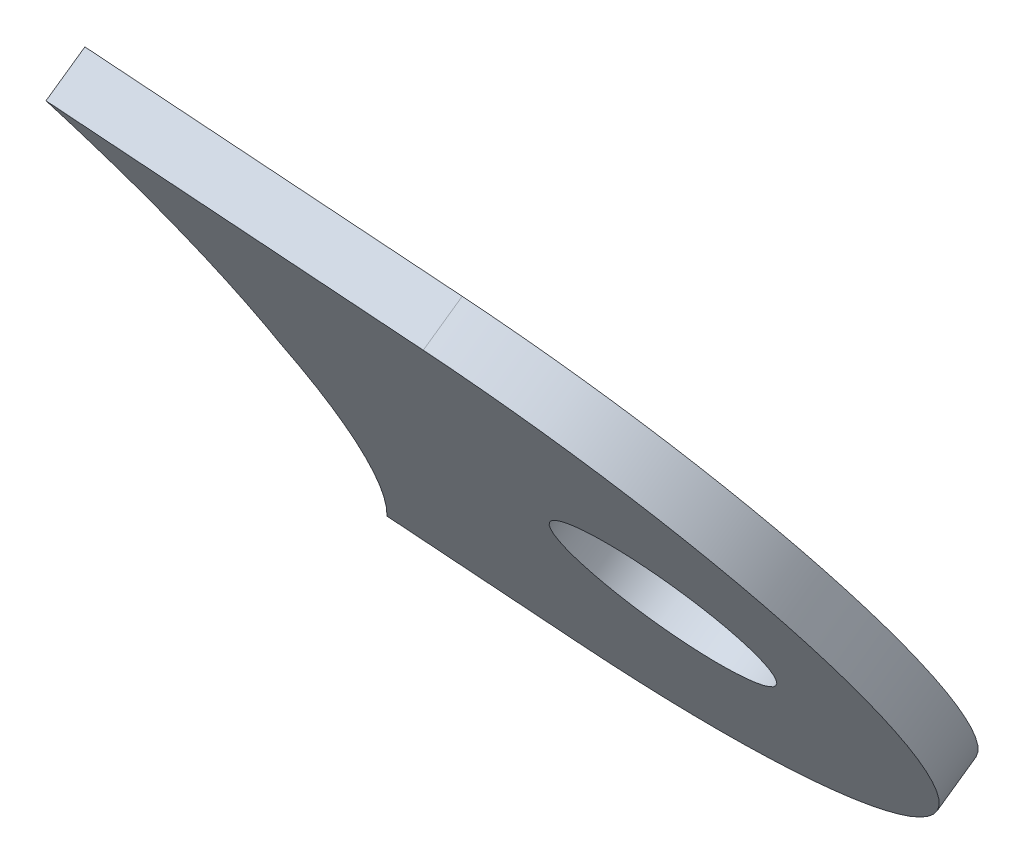
SolidWorks part; units mm, degrees
ref_plane "Front Plane" through (0, 0, 0) normal (0, 0, 1) x (1, 0, 0)
ref_plane "Top Plane" through (0, 0, 0) normal (0, 1, 0) x (1, 0, 0)
ref_plane "Right Plane" through (0, 0, 0) normal (1, 0, 0) x (0, 0, -1)
ref_plane "Plane1" through (0, 220.8127, -315.3533) normal (0, 0.5736, -0.8192) x (-1, 0, 0)
sketch "Sketch1" plane through (0, 220.8127, -315.3533) normal (0, 0.5736, -0.8192) x (-1, 0, 0)
  line L0 (-352.9369, 115.8265) -> (-375.2959, 107.875)
  line L1 (-366.7852, 83.9433) -> (-352.9369, 88.8681)
  line L2 (-352.9369, 88.8681) -> (-352.9369, 115.8265)
  line L3 (-371.0405, 95.9092) -> (-375.5277, 94.3134) construction
  arc A0 (-375.2959, 107.875) -> (-366.7852, 83.9433) centre (-371.0405, 95.9092) ccw
  circle A2 centre (-375.5277, 94.3134) radius 3.302
  point P5 (-352.9369, 102.3473)
  dimension "D1" = 25.4
  dimension "D2" = 4.7625
extrude "Boss-Extrude1" add sketch "Sketch1" along normal blind 1.5875
ref_plane "Plane2" through (364.3517, 343.6254, -135.3997) normal (-0.0893, -0.3048, -0.9482) x (-0.996, 0.0273, 0.085)
sketch "Sketch2" plane through (364.3517, 343.6254, -135.3997) normal (-0.0893, -0.3048, -0.9482) x (-0.996, 0.0273, 0.085)
  circle A0 centre (-0.0378, -0.5075) radius 12.7
  dimension "D1" = 25.4
extrude "Cut-Extrude2" cut sketch "Sketch2" along normal through all
sketch "Sketch3" plane through (0, 221.7233, -316.6537) normal (0, 0.5736, -0.8192) x (-1, 0, 0)
  line L0 (-361.4453, 85.8423) -> (-360.534, 86.1664)
  line L1 (-360.534, 86.1664) -> (-363.8042, 111.9618)
  ellipse E0 centre (-352.6795, 99.4145) end of major axis (-355.0381, 120.3816) minor radius 12.7 (-363.8042, 111.9618) -> (-361.4453, 85.8423) ccw construction
  ellipse E1 centre (-352.6795, 99.4145) end of major axis (-355.0381, 120.3816) minor radius 12.7 (-363.8042, 111.9618) -> (-361.4453, 85.8423) ccw
extrude "Cut-Extrude3" cut sketch "Sketch3" against normal through all
sketch "Sketch5" plane through (0, 220.8127, -315.3533) normal (0, -0.5736, 0.8192) x (1, 0, 0)
  line L1 (364.8196, 111.6006) -> (363.8042, 111.9618)
  line L2 (363.8042, 111.9618) -> (365.4018, 99.043)
  ellipse E1 centre (352.9149, 101.5074) end of major axis (355.2735, 122.4746) minor radius 12.7 (365.4018, 99.043) -> (364.8196, 111.6006) ccw construction
  ellipse E3 centre (352.9149, 101.5074) end of major axis (355.2735, 122.4746) minor radius 12.7 (365.4018, 99.043) -> (364.8196, 111.6006) ccw
extrude "Cut-Extrude4" cut sketch "Sketch5" against normal through all
